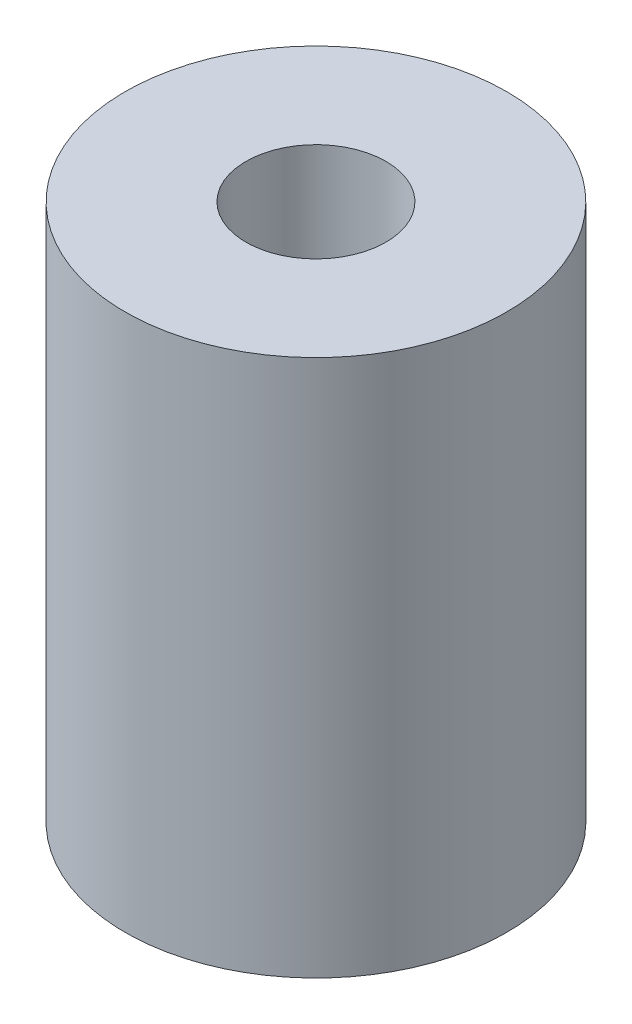
SolidWorks part; units mm, degrees
ref_plane "Front Plane" through (0, 0, 0) normal (0, 0, 1) x (1, 0, 0)
ref_plane "Top Plane" through (0, 0, 0) normal (0, 1, 0) x (1, 0, 0)
ref_plane "Right Plane" through (0, 0, 0) normal (1, 0, 0) x (0, 0, -1)
sketch "Sketch1" plane through (0, 0, 0) normal (0, 1, 0) x (1, 0, 0)
  circle A0 centre (0, 0) radius 15
  dimension "SLEEVE_OD" = 30
extrude "Boss-Extrude1" add sketch "Sketch1" along normal blind 42.2401
sketch "Sketch2" plane through (0, 0, 0) normal (0, 1, 0) x (1, 0, 0)
  circle A0 centre (0, 0) radius 5.5043
  dimension "BORE_D" = 11.0085
extrude "Cut-Extrude1" cut sketch "Sketch2" along normal through all
chamfer "Chamfer1" distance 2.6635 angle 69.374 rebuild error yes
